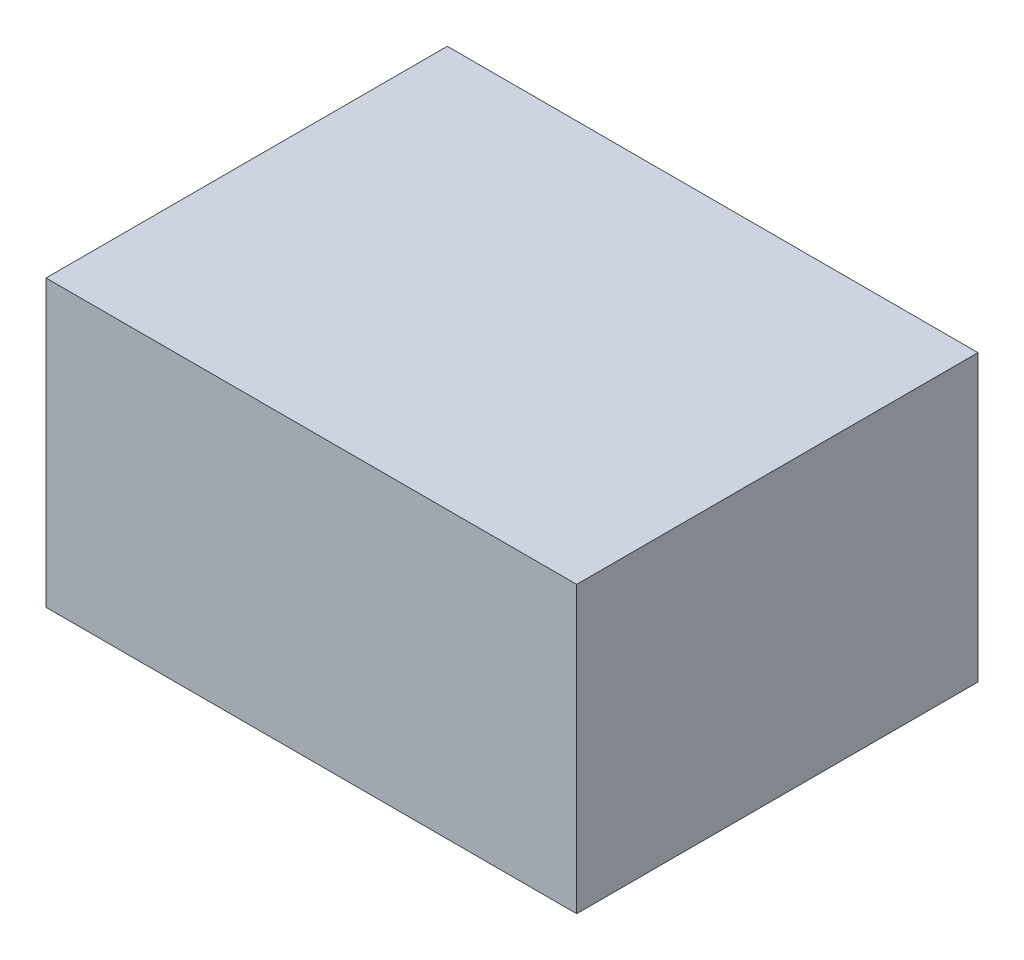
SolidWorks part; units mm, degrees
ref_plane "Front Plane" through (0, 0, 0) normal (0, 0, 1) x (1, 0, 0)
ref_plane "Top Plane" through (0, 0, 0) normal (0, 1, 0) x (1, 0, 0)
ref_plane "Right Plane" through (0, 0, 0) normal (1, 0, 0) x (0, 0, -1)
sketch "Sketch1" plane through (0, 0, 0) normal (0, 1, 0) x (1, 0, 0)
  line L1 (-160, -121) -> (160, -121)
  line L2 (-160, -121) -> (-160, 121)
  line L3 (-160, 121) -> (160, 121)
  line L4 (160, -121) -> (160, 121)
  line L5 (-160, -121) -> (160, 121) construction
  line L6 (-160, 121) -> (160, -121) construction
  point P0 (0, 0)
  dimension "D1" = 320
  dimension "D2" = 242
extrude "Boss-Extrude1" add sketch "Sketch1" along normal blind 172
equation "\"PCLength\"= 320mm'Length across I/O from PS to GPU"
equation "\"PCWidth\"= 242mm'Distance of longest part parallel to GPU(ussually GPU)"
equation "\"PCHeight\"= 172mm'Tallest point with mobo laying flat"
equation "\"WallThickness\"= 9mm'Thickness of each outer tank wall"
equation "\"ThermoBarrierThickness\"= 3mm'Thickness of barrier between hot side and cold side"
equation "\"HotSideGap\"= 40mm'Space in the hot side for a pump"
equation "\"PCClearance\"= 30mm'Clearance from top of tank to top of PC"
equation "\"RadiatorHeight\"= 275mm'Final Height from ground of radiators"
equation "\"D1@Sketch1\"=\"PCLength\""
equation "\"D2@Sketch1\"=\"PCWidth\""
equation "\"D1@Boss-Extrude1\"=\"PCHeight\""
